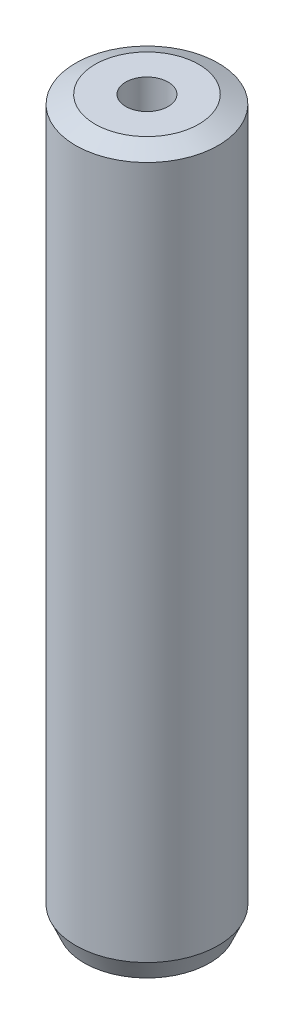
SolidWorks part; units mm, degrees
ref_plane "Front Plane" through (0, 0, 0) normal (0, 0, 1) x (1, 0, 0)
ref_plane "Top Plane" through (0, 0, 0) normal (0, 1, 0) x (1, 0, 0)
ref_plane "Right Plane" through (0, 0, 0) normal (1, 0, 0) x (0, 0, -1)
sketch "Sketch1" plane through (0, 0, 0) normal (0, 1, 0) x (1, 0, 0)
  circle A0 centre (0, 0) radius 42.5
  dimension "SHAFT_OD" = 85
extrude "Boss-Extrude1" add sketch "Sketch1" along normal blind 429.3651
sketch "Sketch2" plane through (0, 0, 0) normal (0, 1, 0) x (1, 0, 0)
  circle A0 centre (0, 0) radius 12.6314
  dimension "BORE_D" = 25.2628
extrude "Cut-Extrude1" cut sketch "Sketch2" along normal through all
chamfer "Chamfer1" distance 5.1534 angle 66.077 2 edges at (0, 429.3651, 42.5) (0, 0, 42.5) first distance on face at (0, 429.3651, 42.5) first distance on face at (0, 0, 12.6314)
